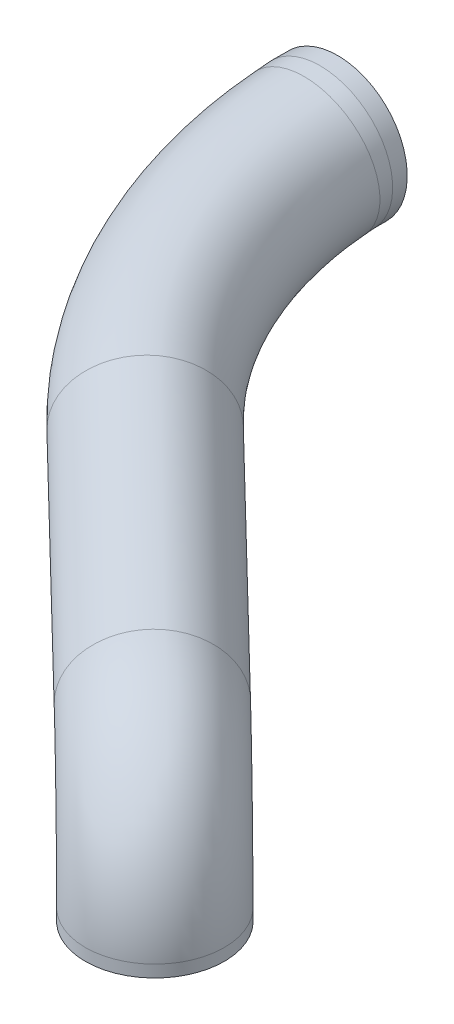
SolidWorks part; units mm, degrees
ref_plane "Front Plane" through (0, 0, 0) normal (0, 0, 1) x (1, 0, 0)
ref_plane "Top Plane" through (0, 0, 0) normal (0, 1, 0) x (1, 0, 0)
ref_plane "Right Plane" through (0, 0, 0) normal (1, 0, 0) x (0, 0, -1)
sketch "Sketch1" plane through (0, 0, 0) normal (0, 0, 1) x (1, 0, 0)
  line L1 (-73.5, 45) -> (0, 45)
  line L2 (-73.5, 45) -> (-73.5, 0)
  line L3 (-73.5, 0) -> (0, 0)
  line L4 (0, 45) -> (0, 0)
  dimension "D1" = 73.5
  dimension "D2" = 45
extrude "Boss-Extrude1" [suppressed] add sketch "Sketch1" along normal blind 89
sketch "Sketch2" [suppressed] plane through (0, 45, 0) normal (0, 1, 0) x (1, 0, 0)
  line L0 (0, -89) -> (-73.5, -89) construction
  line L1 (-73.5, -89) -> (-73.5, 0) construction
  circle A0 centre (-64, -79.5) radius 9.5 construction
  circle A1 centre (-64, -79.5) radius 7
  point P3 (-61.6014, -78.8595)
  dimension "D1" = 19
  dimension "D2" = 14
sketch "Sketch3" [suppressed] plane through (0, 0, 0) normal (0, 0, -1) x (-1, 0, 0)
  line L0 (73.5, 0) -> (0, 0) construction
  line L1 (0, 0) -> (0, 45) construction
  circle A0 centre (9.5, 9.5) radius 7
  circle A1 centre (9.5, 9.5) radius 9.5 construction
  dimension "D1" = 14
  dimension "D2" = 19
sketch3d "3DSketch2" [suppressed]
  line L0 (-64, 45, 79.5) -> (-64, 35, 79.5)
  line L1 (-9.5, 9.5, 0) -> (-9.5, 9.5, 10)
  spline S0 degree 3 poles (-64, 35, 79.5) (-64, 34.9862, 79.5) (-65.2571, 14.1212, 76.1903) (-28.2794, 13.142, 69.1406) (-14.1549, 8.9781, 41.3164) (-9.5, 9.5, 35.1071) (-9.5, 9.5, 10) knots 0 0 0 0 0.331216 0.561157 0.628036 1 1 1 1
  point P7 (-38.5569, 15.6168, 78.324)
  point P8 (-52.0022, 18.7777, 76.1927)
  point P9 (-32.0977, 9.353, 73.1766)
  point P11 (-36.4029, 15.0323, 72.9549)
  point P12 (-55.1511, 24.8773, 77.6238)
  point P13 (-58.5368, 20.0591, 82.2173)
  point P14 (-54.0272, 18.9424, 82.3964)
  point P15 (-33.8881, 12.6607, 73.3214)
  point P16 (-32.3092, 13.4644, 62.6158)
  point P17 (-31.5106, 15.3075, 55.8615)
  point P18 (-31.0964, 12.5816, 55.7916)
  point P19 (0, 0, 0)
  point P20 (-54.3537, 19.3138, 81.15)
  point P21 (-30.2294, 7.1014, 49.3505)
  point P22 (-56.7499, 16.9664, 74.4601)
  point P23 (-23.5275, 8.8007, 59.3306)
  point P24 (0, 0, 0)
  point P25 (-23.6003, 10.647, 59.29)
  point P26 (0, 0, 0)
  point P27 (0, 0, 0)
  point P28 (0, 0, 0)
  point P29 (0, 0, 0)
  point P30 (0, 0, 0)
  point P31 (0, 0, 0)
  point P32 (-53.5355, 17.3197, 74.5516)
  point P33 (0, 0, 0)
  point P34 (0, 0, 0)
  point P35 (-23.357, 11.6371, 59.0752)
  dimension "D1" = 10
  dimension "D2" = 10
sketch3d "3DSketch3"
  line L0 (0, 0, 0) -> (0, 0, -79.5) construction
  line L1 (0, 0, -79.5) -> (0, 26, -79.5) construction
  line L2 (0, 26, -79.5) -> (-54.5, 26, -79.5) construction
  line L3 (-54.5, 26, -79.5) -> (-54.5, 26, -77.5)
  line L4 (0, 0, 0) -> (0, 1.6456, 0)
  line L5 (-54.5, 26, -77.5) -> (-54.5, 25.8458, -75.7374)
  line L6 (-54.5, 26, -79.5) -> (-54.5, -49974, -79.5) construction
  line L7 (-9.5449, 16.5449, -9.2113) -> (-37.8962, 21.1337, -36.5716)
  arc A0 (-9.5449, 16.5449, -9.2113) -> (0, 1.6456, 0) centre (-10.7936, 1.6456, -10.4163) ccw
  arc A1 (-37.8962, 21.1337, -36.5716) -> (-54.5, 25.8458, -75.7374) centre (0.3371, 21.6323, -76.106) ccw
  point P4 (0, 15, 0)
  point P8 (-0.3773, 1.6456, -21.2098)
  point P13 (-54.5, 23.8211, -52.5951)
  point P14 (-3.8924, -32.9961, -80.8854)
  dimension "D1" = 15
  dimension "D2" = 2
  dimension "D3" = 85
  dimension "D4" = 25
  dimension "D8" = 15
  dimension "D5" = 79.5
  dimension "D9" = 55
  dimension "D6" = 54.5
  dimension "D7" = 26
sketch "Sketch9" plane through (0, 0, 0) normal (0, 1, 0) x (1, 0, 0)
  circle A0 centre (0, 0) radius 7
  circle A1 centre (0, 0) radius 9.5
  dimension "D1" = 14
  dimension "D2" = 19
sweep "Sweep2" add profiles "Sketch9" path "3DSketch3"
